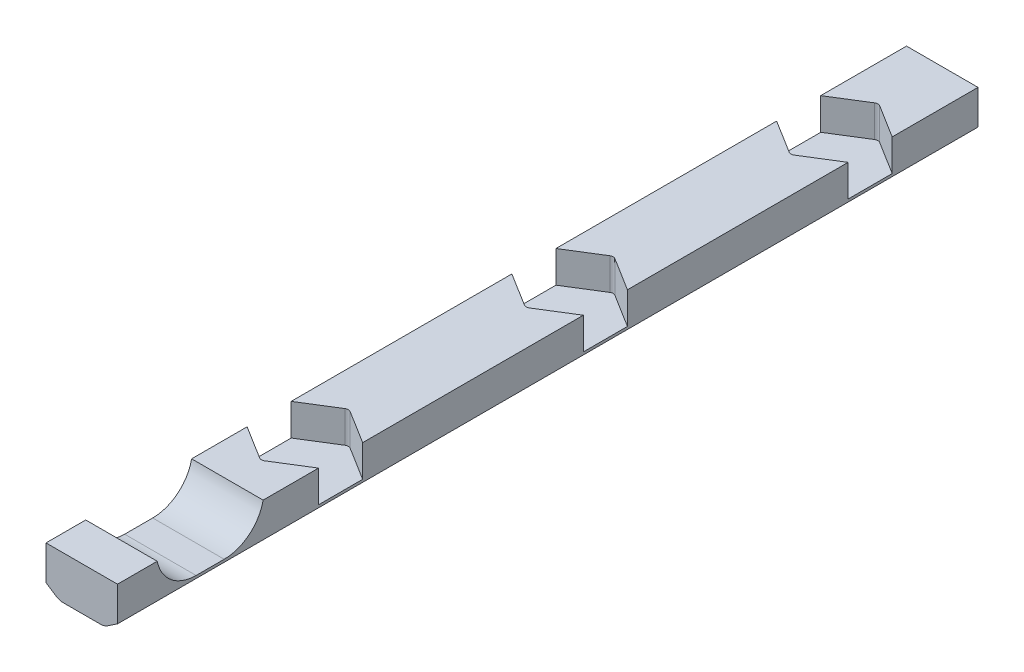
SolidWorks part; units mm, degrees
ref_plane "Front Plane" through (0, 0, 0) normal (0, 0, 1) x (1, 0, 0)
ref_plane "Top Plane" through (0, 0, 0) normal (0, 1, 0) x (1, 0, 0)
ref_plane "Right Plane" through (0, 0, 0) normal (1, 0, 0) x (0, 0, -1)
sketch "Sketch1" plane through (0, 0, 0) normal (0, 0, 1) x (1, 0, 0)
  line L0 (0, 0) -> (3.4, 0)
  line L1 (3.4, 0) -> (4.4, 0.6633)
  line L2 (4.4, 0.6633) -> (4.4, 3.2633)
  line L3 (4.4, 3.2633) -> (-1, 3.2633)
  line L4 (-1, 3.2633) -> (-1, 0.6633)
  line L5 (-1, 0.6633) -> (0, 0)
  dimension "D1" = 5.4
  dimension "D2" = 3.4
  dimension "D3" = 1.2
  dimension "D4" = 2.6
  dimension "D5" = 2.6
  dimension "D6" = 1.2
extrude "Boss-Extrude1" add sketch "Sketch1" along normal blind 65
fillet "Fillet3" radius 1 1 edges at (3.4, 0, 32.5)
fillet "Fillet4" radius 1 1 edges at (0, 0, 32.5)
sketch "Sketch2" plane through (0, 3.2633, 0) normal (0, 1, 0) x (1, 0, 0)
  line L0 (4.4, -9.81) -> (4.4, -6.48)
  line L1 (4.4, -65) -> (4.4, 0) construction
  line L2 (4.4, -6.48) -> (1.7, -4.8)
  line L3 (1.7, -4.8) -> (-1, -6.48)
  line L4 (-1, -65) -> (-1, 0) construction
  line L5 (-1, -6.48) -> (-1, -9.81)
  line L6 (-1, -9.81) -> (1.7, -11.49)
  line L7 (1.7, -11.49) -> (4.4, -9.81)
  line L8 (4.4, 0) -> (-1, 0) construction
  point P4 (0, 0)
  point P11 (0, 0)
  point P12 (-1.1775, -8.7576)
  point P13 (0, 0)
  dimension "D1" = 3.18
  dimension "D2" = 3.18
  dimension "D3" = 3.18
  dimension "D4" = 3.18
  dimension "D5" = 3.33
  dimension "D6" = 5.4
  dimension "D7" = 3.33
  dimension "D8" = 4.8
extrude "Cut-Extrude1" cut sketch "Sketch2" against normal blind 2.4
pattern_linear "LPattern1" count 3 spacing 20 along (0, 0, 1) of "Cut-Extrude1"
sketch "Sketch3" plane through (0, 3.2633, 0) normal (0, 1, 0) x (1, 0, 0)
  line L0 (-1, -65) -> (-1, -49.81) construction
  line L1 (-1, -62) -> (4.4, -62)
  line L2 (-1, -62) -> (-1, -54)
  line L3 (-1, -54) -> (4.4, -54)
  line L4 (4.4, -62) -> (4.4, -54)
  line L5 (4.4, -65) -> (4.4, -49.81) construction
  line L6 (4.4, -65) -> (-1, -65) construction
  dimension "D1" = 3
  dimension "D2" = 8
extrude "Cut-Extrude2" cut sketch "Sketch3" against normal blind 2.4
fillet "Fillet5" radius 3 2 edges at (1.7, 0.8633, 54) (1.7, 0.8633, 62)
fillet "Fillet6" radius 0.35 6 edges at (1.7, 2.0633, 44.8) (1.7, 2.0633, 51.49) (1.7, 2.0633, 24.8) (1.7, 2.0633, 31.49) (1.7, 2.0633, 4.8) (1.7, 2.0633, 11.49)
